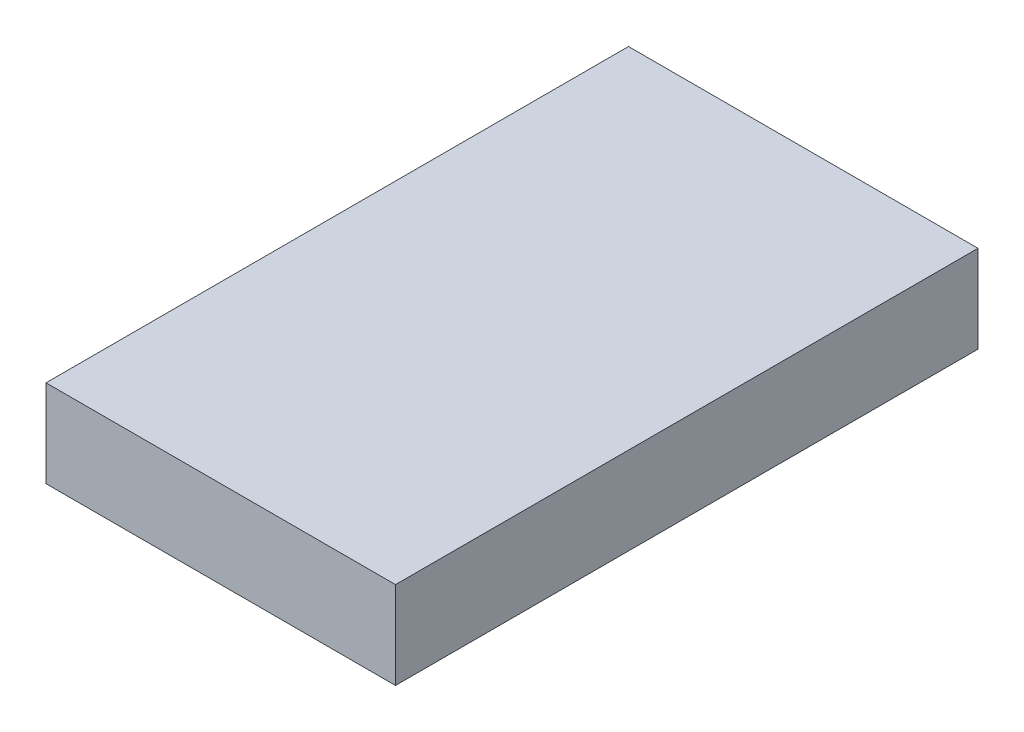
SolidWorks part; units mm, degrees
material "Cast Alloy Steel"
ref_plane "Front Plane" through (0, 0, 0) normal (1, 0, 0) x (0, 1, 0)
ref_plane "Top Plane" through (0, 0, 0) normal (0, 0, 1) x (0, 1, 0)
ref_plane "Right Plane" through (0, 0, 0) normal (0, 1, 0) x (-1, 0, 0)
sketch "Sketch1" plane through (0, 0, 0) normal (1, 0, 0) x (0, 1, 0)
  line L1 (0, -55) -> (0, 55) construction
  line L2 (-450, 150) -> (0, 150)
  line L3 (-450, 150) -> (-450, 0)
  line L4 (-450, 0) -> (0, 0)
  line L5 (0, 150) -> (0, 0)
  line L6 (0, 150) -> (30, 150)
  line L7 (0, 150) -> (0, 350)
  line L8 (0, 350) -> (30, 350)
  line L9 (30, 150) -> (30, 350)
  line L10 (-450, 0) -> (-600, 0)
  line L11 (-450, 0) -> (-450, -500)
  line L12 (-450, -500) -> (-600, -500)
  line L13 (-600, 0) -> (-600, -500)
  line L14 (55, 0) -> (-55, 0) construction
  dimension "D1" = 200
  dimension "D2" = 30
  dimension "D3" = 150
  dimension "D4" = 150
  dimension "D5" = 450
  dimension "D6" = 500
  dimension "D7" = 0
  dimension "D8" = 0
extrude "Boss-Extrude2" add sketch "Sketch1" along normal blind 60 and the other way blind 60 contours L6 L9 L8 L7 | L7 L6 L9 L8 region at (0, 15, 250)
